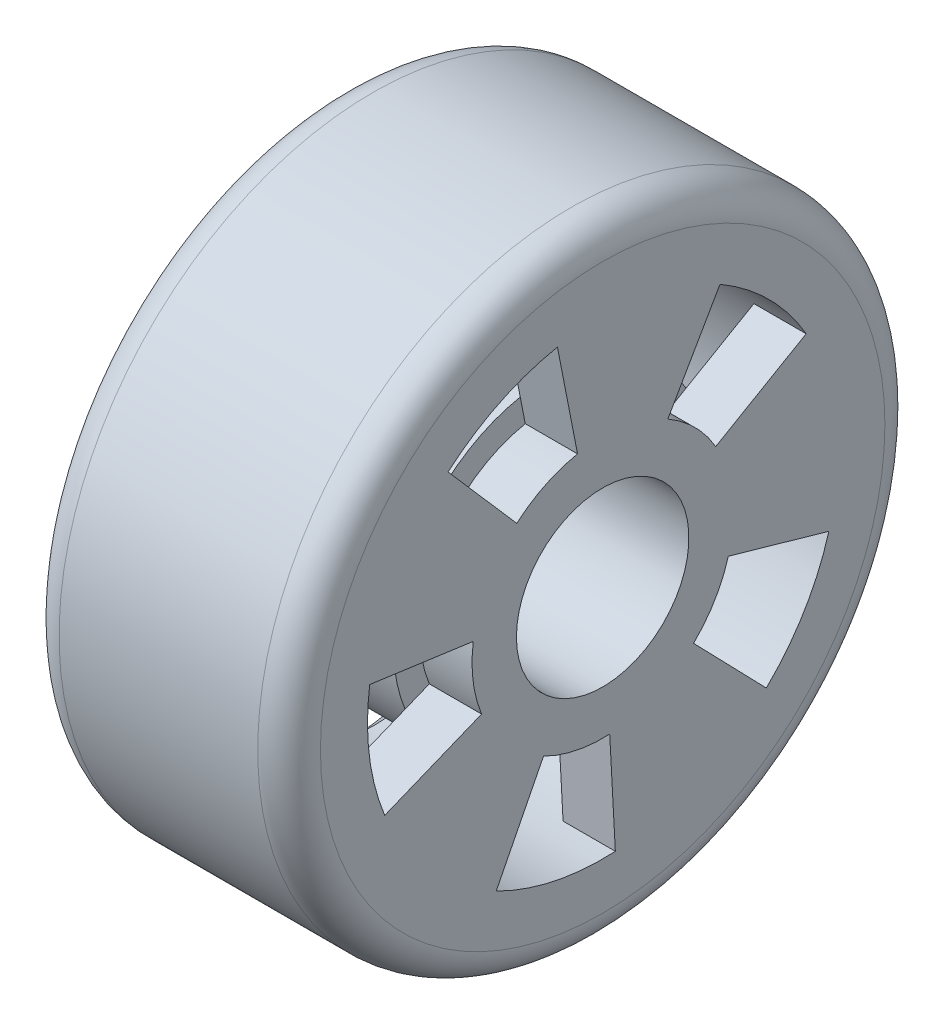
SolidWorks part; units mm, degrees
ref_plane "Front Plane" through (0, 0, 0) normal (0, 0, 1) x (1, 0, 0)
ref_plane "Top Plane" through (0, 0, 0) normal (0, 1, 0) x (1, 0, 0)
ref_plane "Right Plane" through (0, 0, 0) normal (1, 0, 0) x (0, 0, -1)
sketch "Sketch1" plane through (0, 0, 0) normal (1, 0, 0) x (0, 0, -1)
  circle A0 centre (0, 0) radius 30
  dimension "D1" = 60
extrude "Boss-Extrude1" add sketch "Sketch1" along normal blind 25
fillet "Fillet1" radius 3 2 edges at (0, 0, -30) (25, 0, -30)
sketch "Sketch3" plane through (0, 0, 0) normal (-1, 0, 0) x (0, 0, 1)
  circle A0 centre (0, 0) radius 22.5
  dimension "D1" = 45
extrude "Cut-Extrude1" cut sketch "Sketch3" against normal blind 20
chamfer "Chamfer1" distance 3 angle 45 1 edges at (0, 0, 22.5)
sketch "Sketch2" plane through (25, 0, 0) normal (-1, 0, 0) x (0, 0, 1)
  line L0 (-6.2332, 10.835) -> (-11.2197, 19.503)
  line L1 (-10.8156, 6.2668) -> (-19.4681, 11.2803)
  line L2 (-10.8156, 6.2668) -> (0, 0) construction
  line L3 (0, 0) -> (-6.2332, 10.835) construction
  arc A0 (-6.2332, 10.835) -> (-10.8156, 6.2668) centre (0, 0) ccw
  arc A1 (-11.2197, 19.503) -> (-19.4681, 11.2803) centre (0, 0) ccw
  dimension "D1" = 25
  dimension "D2" = 45
  dimension "D3" = 30
extrude "Cut-Extrude2" cut sketch "Sketch2" along normal through all
pattern_circular "CirPattern1" count 5 every 71 about axis through (25, 0, 0) along (1, 0, 0) of "Cut-Extrude2"
sketch "Sketch4" plane through (20, 0, 0) normal (-1, 0, 0) x (0, 0, 1)
  circle A0 centre (0, 0) radius 15
  dimension "D1" = 30
extrude "Boss-Extrude2" add sketch "Sketch4" along normal blind 15
sketch "Sketch5" plane through (5, 0, 0) normal (-1, 0, 0) x (0, 0, 1)
  circle A0 centre (0, 0) radius 8.25
  dimension "D1" = 16.5
extrude "Cut-Extrude3" cut sketch "Sketch5" against normal through all
sketch "Sketch6" plane through (5, 0, 0) normal (-1, 0, 0) x (0, 0, 1)
  circle A0 centre (0, 0) radius 10
  circle A1 centre (0, 0) radius 5
  dimension "D1" = 20
extrude "Boss-Extrude3" add sketch "Sketch6" against normal blind 3
